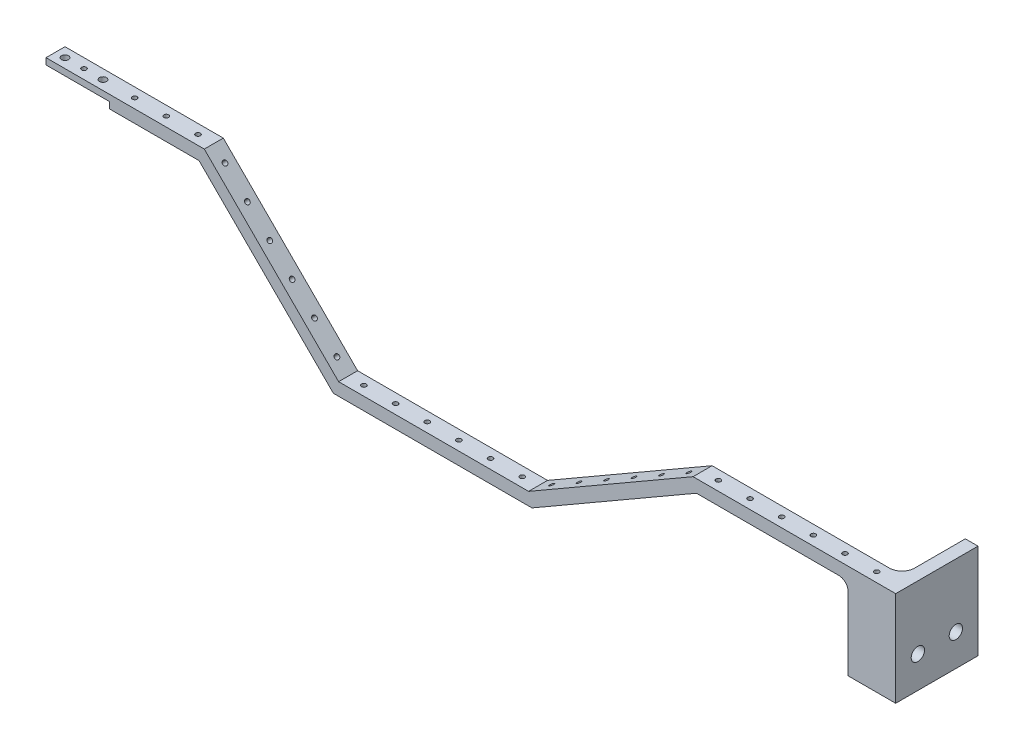
SolidWorks part; units mm, degrees
ref_plane "Front Plane" through (0, 0, 0) normal (0, 0, 1) x (1, 0, 0)
ref_plane "Top Plane" through (0, 0, 0) normal (0, 1, 0) x (1, 0, 0)
ref_plane "Right Plane" through (0, 0, 0) normal (1, 0, 0) x (0, 0, -1)
sketch "Sketch1" plane through (0, 0, 0) normal (0, 0, 1) x (1, 0, 0)
  line L0 (166.5541, -30.9816) -> (166.5541, -0.9816)
  line L1 (166.5541, -0.9816) -> (102.5541, -0.9816)
  line L2 (102.5541, -0.9816) -> (50.5926, -30.9816)
  line L3 (50.5926, -30.9816) -> (-9.4074, -30.9816)
  line L4 (-9.4074, -30.9816) -> (-51.8338, 11.4448)
  line L5 (-51.8338, 11.4448) -> (-101.8338, 11.4448)
  line L6 (166.5541, -30.9816) -> (162.5541, -30.9816)
  line L7 (162.5541, -30.9816) -> (162.5541, -4.9816)
  line L8 (162.5541, -4.9816) -> (103.6259, -4.9816)
  line L9 (103.6259, -4.9816) -> (51.6644, -34.9816)
  line L10 (51.6644, -34.9816) -> (-11.0642, -34.9816)
  line L11 (-11.0642, -34.9816) -> (-53.4906, 7.4448)
  line L12 (-53.4906, 7.4448) -> (-101.8338, 7.4448)
  line L13 (-101.8338, 7.4448) -> (-101.8338, 11.4448)
  dimension "D1" = 30
  dimension "D2" = 64
  dimension "D3" = 60
  dimension "D4" = 150
  dimension "D5" = 60
  dimension "D6" = 60
  dimension "D7" = 50
  dimension "D8" = 135
  dimension "D9" = 4
  dimension "D10" = 4
  dimension "D11" = 4
  dimension "D12" = 4
  dimension "D13" = 4
  dimension "D14" = 4
extrude "Boss-Extrude1" add sketch "Sketch1" along normal blind 6
sketch "Sketch2" plane through (166.5541, 0, 0) normal (1, 0, 0) x (0, 0, -1)
  line L1 (0, -30.9816) -> (20, -30.9816)
  line L2 (0, -30.9816) -> (0, -0.9816)
  line L3 (0, -0.9816) -> (20, -0.9816)
  line L4 (20, -30.9816) -> (20, -0.9816)
  dimension "D1" = 20
extrude "Boss-Extrude2" add sketch "Sketch2" against normal blind 4
sketch "Sketch3" plane through (0, 0, 6) normal (0, 0, 1) x (1, 0, 0)
  line L1 (-101.8338, 7.4448) -> (-81.8338, 7.4448)
  line L2 (-101.8338, 7.4448) -> (-101.8338, 9.4448)
  line L3 (-101.8338, 9.4448) -> (-81.8338, 9.4448)
  line L4 (-81.8338, 7.4448) -> (-81.8338, 9.4448)
  dimension "D1" = 2
  dimension "D2" = 20
extrude "Cut-Extrude1" cut sketch "Sketch3" against normal blind 6
sketch "Sketch4" plane through (0, -0.9816, 0) normal (0, 1, 0) x (1, 0, 0)
  line L0 (162.5541, 0) -> (102.5541, 0) construction
  line L1 (102.5541, -6) -> (102.5541, 0) construction
  circle A0 centre (107.5541, -3) radius 0.75
  circle A2 centre (117.5541, -3) radius 0.75
  circle A4 centre (127.5541, -3) radius 0.75
  circle A6 centre (137.5541, -3) radius 0.75
  circle A8 centre (147.5541, -3) radius 0.75
  circle A10 centre (157.5541, -3) radius 0.75
  circle A11 centre (152.5541, -3) radius 0.75 [skipped]
  circle A12 centre (142.5541, -3) radius 0.75 [skipped]
  circle A13 centre (132.5541, -3) radius 0.75 [skipped]
  circle A14 centre (122.5541, -3) radius 0.75 [skipped]
  circle A15 centre (112.5541, -3) radius 0.75 [skipped]
  dimension "D1" = 1.5
  dimension "D2" = 3
  dimension "D3" = 5
  dimension "D4" = 11
extrude "Cut-Extrude2" cut sketch "Sketch4" against normal through all
sketch "Sketch5" plane through (26.0636, -45.1434, 0) normal (-0.5, 0.866, 0) x (0.866, 0.5, 0)
  line L0 (88.3237, 0) -> (28.3237, 0) construction
  line L1 (28.3237, -6) -> (28.3237, 0) construction
  circle A0 centre (33.3237, -3) radius 0.75
  circle A2 centre (43.3237, -3) radius 0.75
  circle A4 centre (53.3237, -3) radius 0.75
  circle A6 centre (63.3237, -3) radius 0.75
  circle A8 centre (73.3237, -3) radius 0.75
  circle A10 centre (83.3237, -3) radius 0.75
  circle A11 centre (78.3237, -3) radius 0.75 [skipped]
  circle A12 centre (68.3237, -3) radius 0.75 [skipped]
  circle A13 centre (58.3237, -3) radius 0.75 [skipped]
  circle A14 centre (48.3237, -3) radius 0.75 [skipped]
  circle A15 centre (38.3237, -3) radius 0.75 [skipped]
  dimension "D1" = 1.5
  dimension "D2" = 3
  dimension "D3" = 5
  dimension "D4" = 11
extrude "Cut-Extrude3" cut sketch "Sketch5" against normal through all
sketch "Sketch6" plane through (0, -30.9816, 0) normal (0, 1, 0) x (1, 0, 0)
  line L0 (50.5926, -6) -> (-9.4074, -6) construction
  line L1 (50.5926, -6) -> (50.5926, 0) construction
  circle A0 centre (45.5926, -3) radius 0.75
  circle A2 centre (35.5926, -3) radius 0.75
  circle A4 centre (25.5926, -3) radius 0.75
  circle A6 centre (15.5926, -3) radius 0.75
  circle A8 centre (5.5926, -3) radius 0.75
  circle A10 centre (-4.4074, -3) radius 0.75
  circle A11 centre (40.5926, -3) radius 0.75 [skipped]
  circle A12 centre (30.5926, -3) radius 0.75 [skipped]
  circle A13 centre (20.5926, -3) radius 0.75 [skipped]
  circle A14 centre (10.5926, -3) radius 0.75 [skipped]
  circle A15 centre (0.5926, -3) radius 0.75 [skipped]
  dimension "D1" = 1.5
  dimension "D2" = 3
  dimension "D3" = 5
  dimension "D4" = 11
extrude "Cut-Extrude4" cut sketch "Sketch6" against normal through all
sketch "Sketch7" plane through (-20.1945, -20.1945, 0) normal (0.7071, 0.7071, 0) x (0, 0, -1)
  line L0 (-6, -15.2552) -> (0, -15.2552) construction
  line L1 (0, -15.2552) -> (0, 44.7448) construction
  circle A0 centre (-3, -10.2552) radius 0.75
  circle A2 centre (-3, -0.2552) radius 0.75
  circle A4 centre (-3, 9.7448) radius 0.75
  circle A6 centre (-3, 19.7448) radius 0.75
  circle A8 centre (-3, 29.7448) radius 0.75
  circle A10 centre (-3, 39.7448) radius 0.75
  circle A11 centre (-3, -5.2552) radius 0.75 [skipped]
  circle A12 centre (-3, 4.7448) radius 0.75 [skipped]
  circle A13 centre (-3, 14.7448) radius 0.75 [skipped]
  circle A14 centre (-3, 24.7448) radius 0.75 [skipped]
  circle A15 centre (-3, 34.7448) radius 0.75 [skipped]
  dimension "D1" = 1.5
  dimension "D2" = 5
  dimension "D3" = 3
  dimension "D4" = 11
extrude "Cut-Extrude5" cut sketch "Sketch7" against normal through all
fillet "Fillet1" radius 4 2 edges at (162.5541, -2.9816, 0) (162.5541, -4.9816, 3)
sketch "Sketch8" plane through (0, 0, 6) normal (0, 0, 1) x (1, 0, 0)
  line L1 (166.5541, -0.9816) -> (151.5541, -0.9816)
  line L2 (166.5541, -0.9816) -> (166.5541, -30.9816)
  line L3 (166.5541, -30.9816) -> (151.5541, -30.9816)
  line L4 (151.5541, -0.9816) -> (151.5541, -30.9816)
  dimension "D1" = 15
extrude "Boss-Extrude3" add sketch "Sketch8" against normal blind 2
fillet "Fillet2" radius 3 3 edges at (155.0541, -4.9816, 4) (161.3826, -6.1531, 4) (162.5541, -19.9816, 4)
fillet "Fillet3" radius 3 1 edges at (151.5541, -4.9816, 3.5)
sketch "Sketch9" plane through (0, 11.4448, 0) normal (0, 1, 0) x (1, 0, 0)
  line L0 (-51.8338, -6) -> (-101.8338, -6) construction
  line L1 (-51.8338, -6) -> (-51.8338, 0) construction
  circle A0 centre (-56.8338, -3) radius 0.75
  circle A1 centre (-66.8338, -3) radius 0.75
  circle A2 centre (-76.8338, -3) radius 0.75
  dimension "D1" = 1.5
  dimension "D2" = 3
  dimension "D3" = 5
  dimension "D4" = 3
extrude "Cut-Extrude6" cut sketch "Sketch9" against normal blind 12
sketch "Sketch10" plane through (0, 9.4448, 0) normal (0, -1, 0) x (1, 0, 0)
  line L0 (-81.8338, 0) -> (-101.8338, 0) construction
  line L1 (-101.8338, 0) -> (-101.8338, 6) construction
  circle A0 centre (-98.8338, 3) radius 1.1
  dimension "D1" = 2.2
  dimension "D2" = 3
  dimension "D3" = 3
extrude "Cut-Extrude7" cut sketch "Sketch10" against normal blind 12
sketch "Sketch11" plane through (0, 9.4448, 0) normal (0, -1, 0) x (1, 0, 0)
  line L0 (-81.8338, 0) -> (-101.8338, 0) construction
  line L1 (-101.8338, 0) -> (-101.8338, 6) construction
  circle A0 centre (-86.8338, 3) radius 1.1
  dimension "D1" = 2.2
  dimension "D2" = 3
  dimension "D3" = 15
extrude "Cut-Extrude8" cut sketch "Sketch11" against normal blind 12
sketch "Sketch12" plane through (0, 9.4448, 0) normal (0, -1, 0) x (1, 0, 0)
  line L0 (-81.8338, 0) -> (-101.8338, 0) construction
  line L1 (-101.8338, 0) -> (-101.8338, 6) construction
  circle A0 centre (-92.8338, 3) radius 0.75
  dimension "D1" = 1.5
  dimension "D2" = 3
  dimension "D3" = 9
extrude "Cut-Extrude9" cut sketch "Sketch12" against normal blind 12
sketch "Sketch13" plane through (166.5541, 0, 0) normal (1, 0, 0) x (0, 0, -1)
  line L0 (-6, -30.9816) -> (20, -30.9816) construction
  line L1 (-6, -30.9816) -> (-6, -0.9816) construction
  circle A0 centre (1, -20.9816) radius 2.1
  dimension "D1" = 4.2
  dimension "D2" = 10
  dimension "D3" = 7
extrude "Cut-Extrude10" cut sketch "Sketch13" against normal blind 6
sketch "Sketch14" plane through (166.5541, 0, 0) normal (1, 0, 0) x (0, 0, -1)
  line L0 (20, -30.9816) -> (20, -0.9816) construction
  line L1 (-6, -30.9816) -> (20, -30.9816) construction
  circle A0 centre (13, -20.9816) radius 2.1
  dimension "D1" = 4.2
  dimension "D2" = 7
  dimension "D3" = 10
extrude "Cut-Extrude11" cut sketch "Sketch14" against normal blind 6
